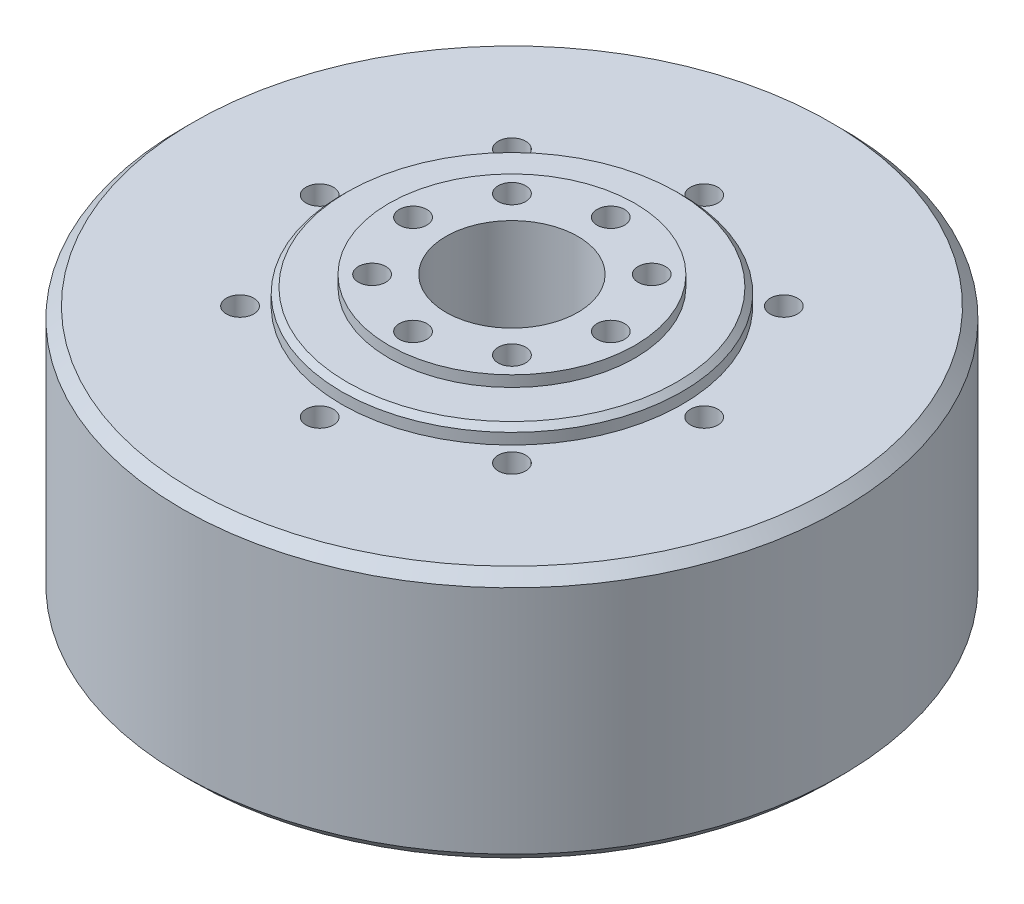
SolidWorks part; units mm, degrees
ref_plane "Front Plane" through (0, 0, 0) normal (0, 0, 1) x (1, 0, 0)
ref_plane "Top Plane" through (0, 0, 0) normal (0, 1, 0) x (1, 0, 0)
ref_plane "Right Plane" through (0, 0, 0) normal (1, 0, 0) x (0, 0, -1)
sketch "Sketch1" plane through (0, 0, 0) normal (0, 1, 0) x (1, 0, 0)
  circle A0 centre (0, 0) radius 60
  dimension "D1" = 120
extrude "Boss-Extrude1" add sketch "Sketch1" along normal blind 46
sketch "Sketch2" plane through (0, 0, 0) normal (0, -1, 0) x (1, 0, 0)
  circle A0 centre (0, 0) radius 32
  dimension "D1" = 64
extrude "Boss-Extrude2" add sketch "Sketch2" along normal blind 12
sketch "Sketch3" plane through (0, 46, 0) normal (0, 1, 0) x (1, 0, 0)
  circle A0 centre (0, 0) radius 31
  dimension "D1" = 62
extrude "Boss-Extrude3" add sketch "Sketch3" along normal blind 3
sketch "Sketch4" plane through (0, 49, 0) normal (0, 1, 0) x (1, 0, 0)
  circle A0 centre (0, 0) radius 22.4
  dimension "D1" = 44.8
extrude "Boss-Extrude4" add sketch "Sketch4" along normal blind 2
sketch "Sketch6" plane through (0, 51, 0) normal (0, 1, 0) x (1, 0, 0)
  circle A0 centre (0, 0) radius 12
  dimension "D1" = 24
extrude "Cut-Extrude1" cut sketch "Sketch6" against normal blind 50
sketch "Sketch8" plane through (0, 51, 0) normal (0, 1, 0) x (1, 0, 0)
  line L0 (0, -65.9774) -> (0, 65.9774) construction
  circle A0 centre (0, 0) radius 18 construction
  circle A1 centre (0, 18) radius 2.5
  circle A2 centre (12.7279, 12.7279) radius 2.5
  circle A3 centre (18, 0) radius 2.5
  circle A4 centre (12.7279, -12.7279) radius 2.5
  circle A5 centre (0, -18) radius 2.5
  circle A6 centre (-12.7279, -12.7279) radius 2.5
  circle A7 centre (-18, 0) radius 2.5
  circle A8 centre (-12.7279, 12.7279) radius 2.5
  point P5 (0, 0)
  dimension "D1" = 36
  dimension "D2" = 8
  dimension "D3" = 5
extrude "Cut-Extrude2" cut sketch "Sketch8" against normal blind 12
sketch "Sketch9" plane through (0, 46, 0) normal (0, 1, 0) x (1, 0, 0)
  line L0 (0, -70.4046) -> (0, 70.4046) construction
  circle A0 centre (0, 0) radius 35 construction
  circle A1 centre (0, 35) radius 2.5
  circle A2 centre (24.7487, 24.7487) radius 2.5
  circle A3 centre (35, 0) radius 2.5
  circle A4 centre (24.7487, -24.7487) radius 2.5
  circle A5 centre (0, -35) radius 2.5
  circle A6 centre (-24.7487, -24.7487) radius 2.5
  circle A7 centre (-35, 0) radius 2.5
  circle A8 centre (-24.7487, 24.7487) radius 2.5
  point P5 (0, 0)
  dimension "D1" = 70
  dimension "D3" = 5
  dimension "D2" = 8
extrude "Cut-Extrude3" cut sketch "Sketch9" against normal through all both and the other way through all
chamfer "Chamfer1" distance 2 angle 45 2 edges at (0, 0, 60) (0, 46, 60)
chamfer "Chamfer2" distance 1 angle 45 2 edges at (0, 49, 31) (0, -12, -32)
ref_axis "Axis1" through (0, -15.15, 0) along (0, 1, 0)
